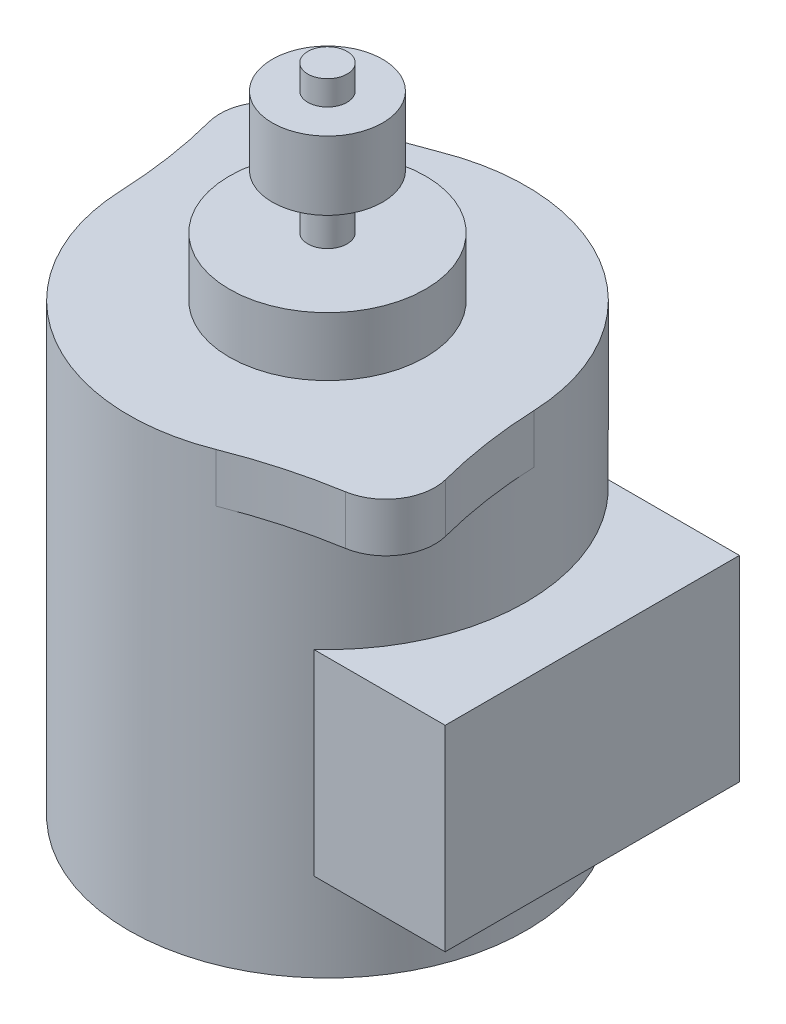
SolidWorks part; units mm, degrees
ref_plane "Front Plane" through (0, 0, 0) normal (0, 0, 1) x (1, 0, 0)
ref_plane "Top Plane" through (0, 0, 0) normal (0, 1, 0) x (1, 0, 0)
ref_plane "Right Plane" through (0, 0, 0) normal (1, 0, 0) x (0, 0, -1)
sketch "Sketch1" plane through (0, 0, 0) normal (0, 1, 0) x (1, 0, 0)
  circle A0 centre (0, 0) radius 4.05
  dimension "D1" = 8.1
extrude "Boss-Extrude1" add sketch "Sketch1" along normal blind 8.1
sketch "Sketch2" plane through (0, 8.1, 0) normal (0, 1, 0) x (1, 0, 0)
  line L0 (-3.3966, 2.2058) -> (3.3966, -2.2058) construction
  line L1 (-8.1053, 0) -> (8.1053, 0) construction
  arc A0 (-3.8335, 1.3063) -> (2.7526, -2.9708) centre (0, 0) ccw
  arc A1 (2.7526, -2.9708) -> (3.8335, -1.3063) centre (3.3966, -2.2058) ccw
  arc A2 (-2.7526, 2.9708) -> (-3.8335, 1.3063) centre (-3.3966, 2.2058) ccw
  circle A3 centre (0, 0) radius 4.05 construction
  arc A4 (3.8335, -1.3063) -> (-2.7526, 2.9708) centre (0, 0) ccw
  point P7 (0, 0)
  point P11 (0, 0)
  dimension "D1" = 8.1
  dimension "D2" = 2
  dimension "D3" = 33
extrude "Boss-Extrude2" add sketch "Sketch2" along normal blind 1
fillet "Fillet1" radius 10 4 edges at (2.7526, 8.6, 2.9708) (3.8335, 8.6, 1.3063) (-2.7526, 8.6, -2.9708) (-3.8335, 8.6, -1.3063)
sketch "Sketch3" plane through (0, 9.1, 0) normal (0, 1, 0) x (1, 0, 0)
  circle A0 centre (0, 0) radius 2
  dimension "D1" = 4
extrude "Boss-Extrude3" add sketch "Sketch3" along normal blind 1.2
sketch "Sketch4" plane through (0, 10.3, 0) normal (0, 1, 0) x (1, 0, 0)
  circle A0 centre (0, 0) radius 0.4
  dimension "D1" = 0.8
extrude "Boss-Extrude4" add sketch "Sketch4" along normal blind 3
sketch "Sketch5" plane through (0, 13.3, 0) normal (0, 1, 0) x (1, 0, 0)
  circle A0 centre (0, 0) radius 1.125
  dimension "D1" = 2.25
extrude "Boss-Extrude5" add sketch "Sketch5" against normal blind 1.4 from offset 0.5 offset against normal yes
ref_plane "Plane1" through (5.4, 0, 0) normal (1, 0, 0) x (0, 0, -1)
sketch "Sketch6" plane through (5.4, 0, 0) normal (1, 0, 0) x (0, 0, -1)
  line L1 (-3, 1.8) -> (3, 1.8)
  line L2 (-3, 1.8) -> (-3, 5.8)
  line L3 (-3, 5.8) -> (3, 5.8)
  line L4 (3, 1.8) -> (3, 5.8)
  line L5 (-3, 1.8) -> (3, 5.8) construction
  line L6 (-3, 5.8) -> (3, 1.8) construction
  point P0 (0, 3.8)
  dimension "D1" = 4
  dimension "D2" = 6
  dimension "D3" = 1.8
extrude "Boss-Extrude6" add sketch "Sketch6" against normal up to next
